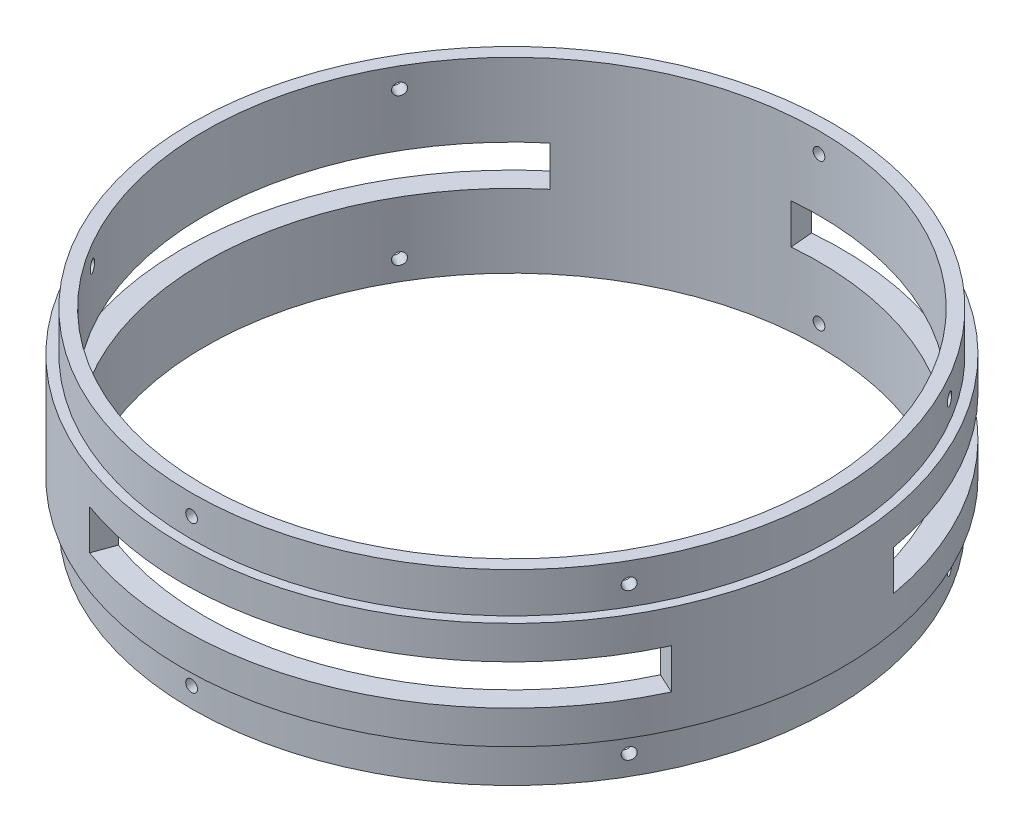
SolidWorks part; units mm, degrees
note: The reader was unsure of these and kept them because the rebuilt part matched: shared geometry of "Sketch1<3>", "Sketch1<4>", "Sketch1<7>".
material "6061-T4 (SS)"
ref_plane "Front Plane" through (0, 0, 0) normal (0, 0, 1) x (1, 0, 0)
ref_plane "Top Plane" through (0, 0, 0) normal (0, 1, 0) x (1, 0, 0)
ref_plane "Right Plane" through (0, 0, 0) normal (1, 0, 0) x (0, 0, -1)
sketch "Sketch1" plane through (0, 0, 0) normal (0, 1, 0) x (1, 0, 0)
  line L0 (0, 0) -> (-6.8294, 78.0608)
  line L1 (0, 0) -> (77.1686, 13.6069)
  line L2 (0, 0) -> (0, 72.1431) construction
  circle A0 centre (0, 0) radius 78.359
  circle A1 centre (0, 0) radius 73.025
  circle A2 centre (0, 0) radius 76.1746
  dimension "D1" = 156.718
  dimension "D2" = 146.05
  dimension "D3" = 152.3492
  dimension "D5" = 80
  dimension "D4" = 85
extrude "Boss-Extrude1" add sketch "Sketch1" along normal blind 25.4 contours L2 A2 L1 A0 | L2 A1 L1 A2 | L2 A2 L1 A1 | L2 A0 L1 A2 | A2 L2 A1 L0 | A0 L2 A2 L0 | A2 L2 A0 L0 | A1 L2 A2 L0
ref_plane "Plane1" through (0, 12.7, 0) normal (0, 1, 0) x (1, 0, 0)
extrude "Boss-Extrude2" add sketch "Sketch1<3>" along normal blind 9.525 from surface at 25.4 contours A2 L2 A1 L0 | L2 A2 L1 A1 | L2 A1 L1 A2 | A1 L2 A2 L0
sketch "Sketch1<3>" plane through (0, 0, 0) normal (0, 1, 0) x (1, 0, 0) same geometry as "Sketch1"
extrude "Boss-Extrude3" add sketch "Sketch1<4>" against normal blind 9.525 contours A2 L2 A1 L0 | A1 L2 A2 L0 | L2 A1 L1 A2 | L2 A2 L1 A1
sketch "Sketch1<4>" plane through (0, 0, 0) normal (0, 1, 0) x (1, 0, 0) same geometry as "Sketch1"
ref_plane "Plane2" through (0, 0, -76.1746) normal (0, 0, -1) x (-1, 0, 0)
ref_axis "Axis1" through (0, 0, 0) along (0, 1, 0)
sketch "Sketch3" plane through (0, 0, -76.1746) normal (0, 0, -1) x (-1, 0, 0)
  line L0 (76.1746, 0) -> (-76.1746, 0) construction
  line L1 (-76.1746, -9.525) -> (76.1746, -9.525) construction
  line L2 (76.1746, 25.4) -> (-76.1746, 25.4) construction
  line L3 (76.1746, 34.925) -> (-76.1746, 34.925) construction
  line L4 (76.1746, 0) -> (-76.1746, 0)
  line L5 (-76.1746, -9.525) -> (76.1746, -9.525)
  line L6 (76.1746, 25.4) -> (-76.1746, 25.4)
  line L7 (76.1746, 34.925) -> (-76.1746, 34.925)
  line L8 (0, 34.925) -> (0, 25.4)
  line L9 (0, 0) -> (0, -9.525)
  circle A0 centre (0, 30.1625) radius 1.397
  circle A1 centre (0, -4.7625) radius 1.397
  point P12 (0, 30.1625)
  point P13 (0, -4.7625)
  point P14 (-77.5445, 179.1871)
  dimension "D1" = 2.794
extrude "Cut-Extrude2" cut sketch "Sketch3" against normal up to next contours L8 A0 | L8 A0 | L9 A1 | L9 A1
extrude "Cut-Extrude3" cut sketch "Sketch1<7>" against normal mid plane 9.525 from surface contours L2 A1 L1 A2 | A1 L2 A2 L0 | A2 L2 A0 L0 | L2 A2 L1 A0
sketch "Sketch1<7>" plane through (0, 0, 0) normal (0, 1, 0) x (1, 0, 0) same geometry as "Sketch1"
pattern_circular "CirPattern2" count 3 over 360 about axis through (0, 0, 0) along (0, 1, 0) of "Cut-Extrude3"
ref_plane "Plane3" through (0, 7.9375, 0) normal (0, 1, 0) x (1, 0, 0)
pattern_circular "CirPattern4" count 3 over 360 about axis through (0, 0, 0) along (0, 1, 0) of "Cut-Extrude2"
sketch "Sketch4" plane through (0, 7.9375, 0) normal (0, 1, 0) x (1, 0, 0)
  circle A0 centre (0, 0) radius 73.025
sketch "Sketch6" plane through (0, 0, 0) normal (0, 0, 1) x (1, 0, 0)
  line L0 (0, -9.5132) -> (0, 34.5654) construction
pattern_circular "CirPattern3" count 6 over 360 about axis through (0, -9.5132, 0) along (0, 1, 0) of "Cut-Extrude2"
equation "\"AB_Coupler_OD_Length\"= 1in"
equation "\"AB_Coupling_Section_Length\"= 0.375in"
equation "\"AB_Coupler_Length\"= \"AB_Coupler_OD_Length\" + \"AB_Coupling_Section_Length\" * 2"
equation "\"D1@Boss-Extrude2\"=\"AB_Coupling_Section_Length\""
equation "\"D1@Boss-Extrude3\"=\"AB_Coupling_Section_Length\""
equation "\"D1@Boss-Extrude1\" = \"AB_Coupler_OD_Length\""
equation "\"Cutout_Angle\" = 80"
equation "\"AB_Coupler_Num_Screws\"= 6"
equation "\"Num_Cutouts\" = 3"
equation "\"D1@CirPattern2\"=\"Num_Cutouts\""
equation "\"D1@CirPattern3\"=\"AB_Coupler_Num_Screws\""
equation "\"AB_Coupler_OD\"= 6.17in"
equation "\"AB_Coupler_ID\"= 5.75in"
equation "\"AB_Coupler_Surface_Diameter\"= 5.998in"
equation "\"D3@Sketch1\"=\"AB_Coupler_Surface_Diameter\""
equation "\"D2@Sketch1\"=\"AB_Coupler_ID\""
equation "\"D1@Sketch1\"=\"AB_Coupler_OD\""
equation "\"AB_Coupling_Screw_Diameter\"= 0.1065in"
equation "\"Aft_Section_Length\"= 40in"
equation "\"Aft_Lower_Length\"= 20in"
equation "\"Aft_Upper_Length\"= \"Aft_Section_Length\" - \"Aft_Lower_Length\" - \"AB_Coupler_OD_Length\""
equation "\"Mid_Coupler_Length\" = 10in"
equation "\"Lead_Screw_Dist\" = 2.25in"
equation "\"Lead_Screw_Diam\" = (27/64)*1in"
equation "\"Lead_Screw_Length\" = (\"Mid_Coupler_Length\" + 2*0.375in + 2*0.5in)"
equation "\"Bodytube_OD\" = 6.17in"
equation "\"Paddle_Pin_Offset\" = .25in"
equation "\"D3@Sketch5\"=\"Paddle_Pin_Offset\""
equation "\"D1@CirPattern4\"=\"Num_Cutouts\""
equation "\"Bodytube_ID\" = 5.998in"
equation "\"Paddle_Pin_Radius\" = 2.55in"
equation "\"D2@Sketch5\"=\"Paddle_Pin_Radius\""
